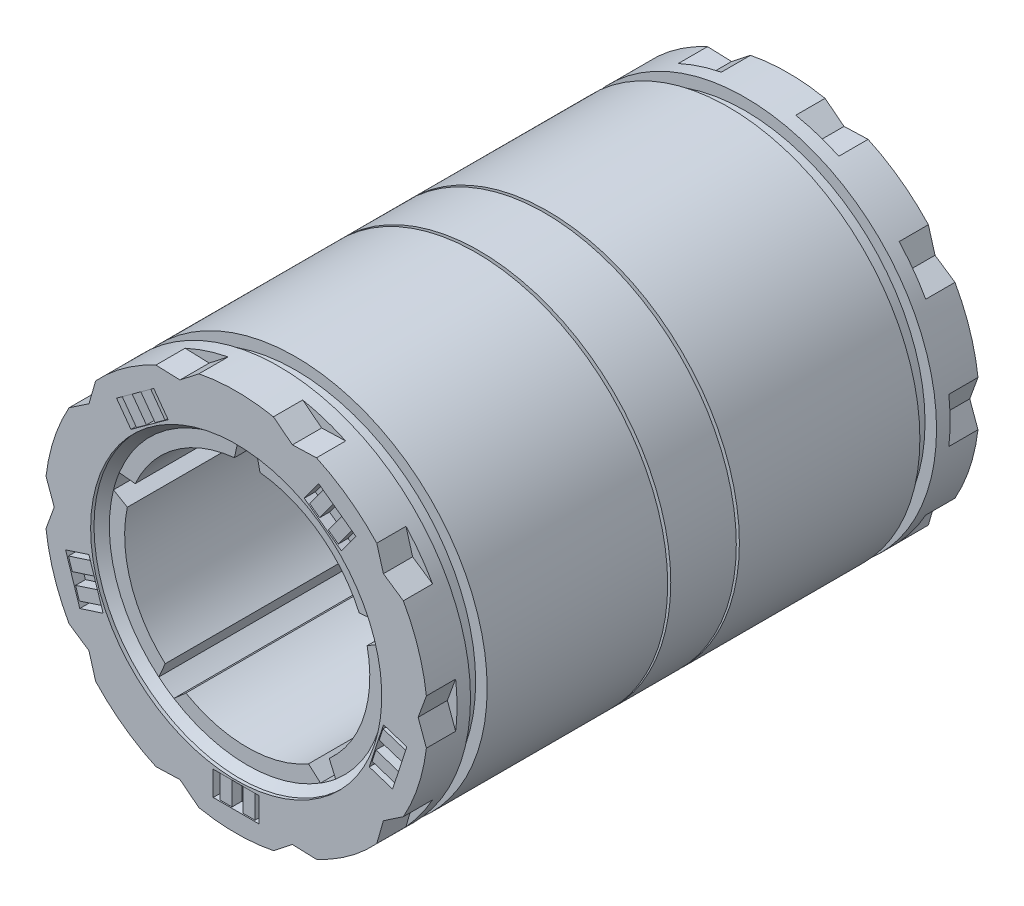
SolidWorks part; units mm, degrees
material "POM Acetal Copolymer"
ref_plane "Front Plane" through (0, 0, 0) normal (0, 0, 1) x (1, 0, 0)
ref_plane "Top Plane" through (0, 0, 0) normal (0, 1, 0) x (1, 0, 0)
ref_plane "Right Plane" through (0, 0, 0) normal (1, 0, 0) x (0, 0, -1)
sketch "Sketch1" plane through (0, 0, 0) normal (0, 0, 1) x (1, 0, 0)
  line L0 (0, 0) -> (-9.9219, -17.1852) construction
  line L2 (9.9219, -17.1852) -> (0, 0) construction
  circle A0 centre (0, 0) radius 19.8438
  circle A1 centre (0, 0) radius 12.7
  point P4 (-6.35, -10.9985)
  point P5 (6.35, -10.9985)
  dimension "OD" = 39.6875
  dimension "ID" = 25.4
  dimension "a" = 60
  dimension "Width" = 12.7
sketch "Sketch2" plane through (0, 0, 0) normal (1, 0, 0) x (0, 0, -1)
  line L0 (-28.575, 0) -> (28.575, 0) construction
  line L1 (0, -19.8438) -> (0, 19.8438) construction
  line L3 (-24.1427, 19.8438) -> (-22.4155, 19.8438)
  line L4 (-24.1427, 19.8438) -> (-24.1427, 18.6499)
  line L5 (-24.1427, 18.6499) -> (-22.4155, 18.6499)
  line L6 (-22.4155, 19.8438) -> (-22.4155, 18.6499)
  point P3 (-24.1427, 0)
  point P5 (24.1427, 0)
  point P10 (-22.4155, 0)
  dimension "Overall Length" = 57.15
  dimension "Retaining Ring Groove End to End Length" = 48.2854
  dimension "Groove Thickness" = 1.7272
  dimension "Groove Depth" = 1.1938
sketch "Sketch3" plane through (0, 0, 0) normal (1, 0, 0) x (0, 0, -1)
  line L0 (-28.575, 12.7) -> (-28.575, 19.8438)
  line L1 (-28.575, 19.8438) -> (-24.1427, 19.8438)
  line L2 (-24.1427, 19.8438) -> (-24.1427, 18.6499)
  line L3 (-24.1427, 18.6499) -> (-22.4155, 18.6499)
  line L4 (-22.4155, 18.6499) -> (-22.4155, 19.8438)
  line L5 (-22.4155, 19.8438) -> (-3.7148, 19.8438)
  line L6 (22.4155, 19.8438) -> (22.4155, 18.65)
  line L7 (22.4155, 18.65) -> (24.1427, 18.65)
  line L8 (24.1427, 18.65) -> (24.1427, 19.8438)
  line L9 (24.1427, 19.8438) -> (28.575, 19.8438)
  line L10 (28.575, 19.8438) -> (28.575, 12.7)
  line L11 (28.575, 12.7) -> (-28.575, 12.7)
  line L14 (-3.7148, 19.8438) -> (-3.7148, 19.05)
  line L15 (-3.7148, 19.05) -> (-3.3947, 19.05)
  line L16 (-3.3947, 19.05) -> (-3.3947, 19.8438)
  line L17 (3.3947, 19.8438) -> (3.3947, 19.05)
  line L18 (3.3947, 19.05) -> (3.7147, 19.05)
  line L19 (3.7147, 19.05) -> (3.7147, 19.8438)
  line L20 (-3.3947, 19.8438) -> (3.3947, 19.8438)
  line L21 (3.7147, 19.8438) -> (22.4155, 19.8438)
  point P17 (0, 12.7)
  point P30 (0, 19.8438)
  dimension "D1" = 7.4295
  dimension "D2" = 0.7937
  dimension "D3" = 0.32
revolve "Revolve1" add sketch "Sketch3" angle 360 about L0
sketch "Sketch4" plane through (0, 0, 0) normal (0, 0, 1) x (1, 0, 0)
  line L0 (-6.35, -10.9985) -> (-7.5961, -12.1009)
  line L2 (-12.4225, 2.6405) -> (-13.856, 3.4849)
  line L3 (6.35, -10.9985) -> (7.5961, -12.1009)
  line L5 (-8.498, -9.4379) -> (-9.1614, -10.9637)
  line L6 (-1.3275, 12.6304) -> (-0.9674, 14.2547)
  line L7 (-11.602, 5.1656) -> (-13.2581, 5.325)
  line L8 (11.602, 5.1656) -> (13.2581, 5.325)
  line L9 (1.3275, 12.6304) -> (0.9674, 14.2547)
  line L10 (8.498, -9.4379) -> (9.1614, -10.9637)
  line L11 (12.4225, 2.6405) -> (13.856, 3.4849)
  arc A0 (0.9674, 14.2547) -> (-0.9674, 14.2547) centre (0, 0) ccw
  circle A1 centre (0, 0) radius 12.7 construction
  arc A2 (-11.602, 5.1656) -> (-12.4225, 2.6405) centre (0, 0) ccw
  arc A11 (-13.2581, 5.325) -> (-13.856, 3.4849) centre (0, 0) ccw
  arc A12 (-13.856, 3.4849) -> (-9.1614, -10.9637) centre (0, 0) ccw construction
  arc A13 (9.1614, -10.9637) -> (13.856, 3.4849) centre (0, 0) ccw construction
  arc A14 (13.2581, 5.325) -> (0.9674, 14.2547) centre (0, 0) ccw construction
  arc A15 (8.498, -9.4379) -> (12.4225, 2.6405) centre (0, 0) ccw construction
  arc A16 (11.602, 5.1656) -> (1.3275, 12.6304) centre (0, 0) ccw construction
  arc A17 (-1.3275, 12.6304) -> (-11.602, 5.1656) centre (0, 0) ccw construction
  arc A18 (-12.4225, 2.6405) -> (-8.498, -9.4379) centre (0, 0) ccw construction
  arc A19 (-0.9674, 14.2547) -> (-13.2581, 5.325) centre (0, 0) ccw construction
  arc A20 (13.856, 3.4849) -> (13.2581, 5.325) centre (0, 0) ccw
  arc A21 (7.5961, -12.1009) -> (9.1614, -10.9637) centre (0, 0) ccw
  arc A22 (-9.1614, -10.9637) -> (-7.5961, -12.1009) centre (0, 0) ccw
  arc A23 (1.3275, 12.6304) -> (-1.3275, 12.6304) centre (0, 0) ccw
  arc A24 (12.4225, 2.6405) -> (11.602, 5.1656) centre (0, 0) ccw
  arc A25 (6.35, -10.9985) -> (8.498, -9.4379) centre (0, 0) ccw
  arc A26 (-8.498, -9.4379) -> (-6.35, -10.9985) centre (0, 0) ccw
  point P31 (0, 0)
  dimension "D1" = 1.5875
  dimension "D3" = 25
  dimension "D2" = 5
extrude "Cut-Extrude1" cut sketch "Sketch4" against normal through all both and the other way through all
sketch "Sketch5" plane through (0, 0, 0) normal (0, 0, 1) x (1, 0, 0)
  circle A0 centre (0, 0) radius 15.0813
  circle A1 centre (0, 0) radius 12.7 construction
  dimension "D1" = 2.3813
extrude "Cut-Extrude2" cut sketch "Sketch5" against normal blind 1.143 from surface starting at face at (0, 0, 28.575)
extrude "Cut-Extrude3" cut sketch "Sketch5<2>" along normal blind 1.143 from surface starting at face at (19.8438, 0, -28.575)
sketch "Sketch5<2>" plane through (0, 0, 0) normal (0, 0, 1) x (1, 0, 0) same geometry as "Sketch5"
chamfer "Chamfer1" distance 0.7937 angle 45 2 edges at (-15.0813, 0, 27.432) (15.0813, 0, -27.432)
sketch "Sketch8" plane through (0, 0, 0) normal (0, 0, 1) x (1, 0, 0)
  line L0 (-8.3186, 18.016) -> (-5.8255, 17.9289)
  line L1 (-5.8255, 17.9289) -> (-3.8596, 19.4648)
  line L2 (0, 0) -> (0, 18.8516) construction
  line L3 (0, 0) -> (-5.8255, 17.9289) construction
  line L4 (3.8596, 19.4648) -> (5.8255, 17.9289)
  line L5 (5.8255, 17.9289) -> (8.3186, 18.016)
  line L6 (14.5636, 13.4787) -> (15.2512, 11.0807)
  line L7 (15.2512, 11.0807) -> (17.3194, 9.6857)
  line L8 (19.7048, 2.3442) -> (18.8516, 0)
  line L9 (18.8516, 0) -> (19.7048, -2.3442)
  line L10 (17.3194, -9.6857) -> (15.2512, -11.0807)
  line L11 (15.2512, -11.0807) -> (14.5636, -13.4787)
  line L12 (8.3186, -18.016) -> (5.8255, -17.9289)
  line L13 (5.8255, -17.9289) -> (3.8596, -19.4648)
  line L14 (-3.8596, -19.4648) -> (-5.8255, -17.9289)
  line L15 (-5.8255, -17.9289) -> (-8.3186, -18.016)
  line L16 (-14.5636, -13.4787) -> (-15.2512, -11.0807)
  line L17 (-15.2512, -11.0807) -> (-17.3194, -9.6857)
  line L18 (-19.7048, -2.3442) -> (-18.8516, 0)
  line L19 (-18.8516, 0) -> (-19.7048, 2.3442)
  line L20 (-17.3194, 9.6857) -> (-15.2512, 11.0807)
  line L21 (-15.2512, 11.0807) -> (-14.5636, 13.4787)
  circle A0 centre (0, 0) radius 19.8438 construction
  circle A1 centre (0, 0) radius 18.8516 construction
  arc A2 (-3.8596, 19.4648) -> (-8.3186, 18.016) centre (0, 0) ccw
  arc A3 (8.3186, 18.016) -> (3.8596, 19.4648) centre (0, 0) ccw
  arc A4 (17.3194, 9.6857) -> (14.5636, 13.4787) centre (0, 0) ccw
  arc A5 (19.7048, -2.3442) -> (19.7048, 2.3442) centre (0, 0) ccw
  arc A6 (14.5636, -13.4787) -> (17.3194, -9.6857) centre (0, 0) ccw
  arc A7 (3.8596, -19.4648) -> (8.3186, -18.016) centre (0, 0) ccw
  arc A8 (-8.3186, -18.016) -> (-3.8596, -19.4648) centre (0, 0) ccw
  arc A9 (-17.3194, -9.6857) -> (-14.5636, -13.4787) centre (0, 0) ccw
  arc A10 (-19.7048, 2.3442) -> (-19.7048, -2.3442) centre (0, 0) ccw
  arc A11 (-14.5636, 13.4787) -> (-17.3194, 9.6857) centre (0, 0) ccw
  point P38 (0, 0)
  dimension "D1" = 140
  dimension "D2" = 0.9922
  dimension "D3" = 10
extrude "Cut-Extrude5" cut sketch "Sketch8" against normal blind 3.029 from surface starting at face at (-15.0813, 0, 28.575)
extrude "Cut-Extrude6" cut sketch "Sketch8<2>" along normal blind 3.029 from surface starting at face at (15.0813, 0, -28.575)
sketch "Sketch8<2>" plane through (0, 0, 0) normal (0, 0, 1) x (1, 0, 0) same geometry as "Sketch8"
sketch "Sketch9" plane through (0, 0, 0) normal (0, 0, 1) x (1, 0, 0)
  line L0 (0, -19.8438) -> (0, -17.8117) construction
  line L1 (-2.3813, -15.2718) -> (-1.8256, -15.2718)
  line L2 (-2.3813, -15.2718) -> (-2.3813, -17.8117)
  line L3 (-2.3813, -17.8117) -> (-1.8256, -17.8117)
  line L4 (2.3813, -15.2718) -> (2.3813, -17.8117)
  line L5 (-1.8256, -15.2718) -> (-1.8256, -17.8117)
  line L6 (-2.3813, -16.5418) -> (-1.8256, -16.5418) construction
  line L7 (-0.5556, -15.2718) -> (-0.5556, -17.8117)
  line L8 (-1.8256, -16.5418) -> (-0.5556, -16.5418) construction
  line L9 (0.5556, -15.2718) -> (0.5556, -17.8117)
  line L10 (-0.5556, -16.5418) -> (0, -16.5418) construction
  line L11 (1.8256, -15.2718) -> (1.8256, -17.8117)
  line L12 (0.5556, -16.5418) -> (1.8256, -16.5418) construction
  line L13 (1.8256, -16.5418) -> (2.3813, -16.5418) construction
  line L14 (0, -16.5418) -> (0.5556, -16.5418) construction
  line L15 (-0.5556, -15.2718) -> (0.5556, -15.2718)
  line L16 (1.8256, -15.2718) -> (2.3813, -15.2718)
  line L17 (1.8256, -17.8117) -> (2.3813, -17.8117)
  line L18 (-0.5556, -17.8117) -> (0.5556, -17.8117)
  circle A1 centre (0, 0) radius 19.8438 construction
  dimension "D1" = 4.7625
  dimension "D2" = 2.54
  dimension "D3" = 2.032
  dimension "D4" = 1.27
extrude "Cut-Extrude7" cut sketch "Sketch9" against normal blind 1.143 from surface starting at face at (-15.0813, 0, 28.575)
sketch "Sketch10" plane through (0, 0, 0) normal (0, 0, 1) x (1, 0, 0)
  line L1 (-2.3813, -15.2718) -> (2.3812, -15.2718)
  line L2 (-2.3813, -15.2718) -> (-2.3812, -17.8117)
  line L3 (-2.3812, -17.8117) -> (2.3813, -17.8117)
  line L4 (2.3812, -15.2718) -> (2.3813, -17.8117)
extrude "Cut-Extrude8" cut sketch "Sketch10" against normal blind 0.127 from surface starting at face at (-2.1034, -16.5418, 28.575)
extrude "Cut-Extrude9" cut sketch "Sketch9<2>" along normal blind 1.143 from surface starting at face at (15.0813, 0, -28.575)
sketch "Sketch9<2>" plane through (0, 0, 0) normal (0, 0, 1) x (1, 0, 0) same geometry as "Sketch9"
extrude "Cut-Extrude11" cut sketch "Sketch10<2>" along normal blind 0.127 from surface starting at face at (2.1034, -16.5418, -28.575)
sketch "Sketch10<2>" plane through (0, 0, 0) normal (0, 0, 1) x (1, 0, 0) same geometry as "Sketch10"
pattern_circular "CirPattern2" count 5 over 360 about axis through (0, 0, 28.575) along (0, 0, 1) of "Cut-Extrude7", "Cut-Extrude8", "Cut-Extrude9", "Cut-Extrude11"
sketch "Sketch6" [suppressed] plane through (0, 0, 0) normal (0, 1, 0) x (1, 0, 0)
  line L0 (-2.54, 21.6535) -> (-2.54, -21.6535)
  line L1 (-3.81, 21.6535) -> (-3.81, -21.6535)
  line L2 (-3.81, -22.9235) -> (-3.81, -21.6535) construction
  line L3 (-2.54, 0) -> (-3.81, 0) construction
  line L4 (-6.35, 0) -> (-3.175, 0) construction
  line L5 (-6.35, 27.432) -> (-6.35, -27.432) construction
  line L6 (-3.175, 0) -> (0, 0) construction
  line L7 (0, 0) -> (3.175, 0) construction
  line L8 (3.175, 0) -> (6.35, 0) construction
  line L9 (6.35, 27.432) -> (6.35, -27.432) construction
  line L10 (0, -28.575) -> (0, 28.575) construction
  line L11 (0, -28.575) -> (0, 28.575) construction
  line L12 (2.54, 0) -> (3.81, 0) construction
  line L13 (3.81, -22.9235) -> (3.81, -21.6535) construction
  line L14 (3.81, 21.6535) -> (3.81, -21.6535)
  line L15 (2.54, 21.6535) -> (2.54, -21.6535)
  arc A0 (-3.81, -21.6535) -> (-3.81, -22.9235) centre (-3.81, -22.2885) ccw
  arc A1 (-2.54, -21.6535) -> (-3.81, -22.9235) centre (-3.81, -21.6535) cw
  arc A2 (-3.81, 21.6535) -> (-3.81, 22.9235) centre (-3.81, 22.2885) cw
  arc A3 (-2.54, 21.6535) -> (-3.81, 22.9235) centre (-3.81, 21.6535) ccw
  arc A4 (2.54, 21.6535) -> (3.81, 22.9235) centre (3.81, 21.6535) cw
  arc A5 (3.81, 21.6535) -> (3.81, 22.9235) centre (3.81, 22.2885) ccw
  arc A6 (2.54, -21.6535) -> (3.81, -22.9235) centre (3.81, -21.6535) ccw
  arc A7 (3.81, -21.6535) -> (3.81, -22.9235) centre (3.81, -22.2885) cw
  point P7 (-2.54, 0)
  point P8 (-3.81, 0)
  point P11 (-3.175, 0)
  dimension "D1" = 1.27
  dimension "D2" = 22.2885
extrude "Cut-Extrude4" [suppressed] cut sketch "Sketch6" against normal up to surface (14.0599 mm away)
sketch "Sketch7" [suppressed] plane through (0, 0, 0) normal (0, 0, 1) x (1, 0, 0)
  line L0 (0, -12.7) -> (0, -14.2875) construction
  line L1 (-2.54, 0) -> (-2.54, -13.2525) construction
  line L2 (-3.81, 0) -> (-3.81, -12.9447) construction
  line L3 (-3.81, -12.9447) -> (-3.1787, -13.114) construction
  line L4 (-3.1787, -13.114) -> (-2.54, -13.2525) construction
  line L6 (-3.9366, -12.878) -> (-2.4045, -13.2889)
  line L8 (-3.1787, -13.114) -> (-3.1705, -13.0834) construction
  circle A0 centre (0, 0) radius 13.4938 construction
  arc A1 (-6.35, -10.9985) -> (6.35, -10.9985) centre (0, 0) ccw construction
  arc A2 (-7.5961, -12.1009) -> (7.5961, -12.1009) centre (0, 0) ccw construction
  circle A3 centre (-3.1787, -13.114) radius 0.7937 construction
  arc A5 (-2.4045, -13.2889) -> (-3.9366, -12.878) centre (-3.1787, -13.114) ccw
  point P11 (0, -13.4938)
revolve "Revolve3" [suppressed] add sketch "Sketch7" angle 360 about L6
pattern_linear "LPattern1" [suppressed] count 15 spacing 1.5875 along (0, 0, 1) count 15 spacing 1.5875 along (0, 0, -1) of bodies 110
mirror "Mirror1" [suppressed] about plane through (0, 0, 0) normal (1, 0, 0)
pattern_circular "CirPattern1" [suppressed] count 5 over 360 about axis through (0, 0, 28.575) along (0, 0, -1) of bodies 112
equation "\"D1@Sketch3\"=\"Overall Length@Sketch2\"*.13"
equation "\"D2@Sketch3\"=\"OD@Sketch1\"*.02"
equation "\"D3@Sketch3\"=\"Overall Length@Sketch2\"*.0056"
equation "\"D1@Sketch4\"=\"OD@Sketch1\"*.04"
equation "\"D1@Sketch5\"=\"OD@Sketch1\"*.06"
equation "\"D1@Cut-Extrude2\"=.02*\"Overall Length@Sketch2\""
equation "\"D1@Cut-Extrude3\"=.02*\"Overall Length@Sketch2\""
equation "\"D1@Sketch6\"= .08*.4*\"OD@Sketch1\""
equation "\"D2@Sketch6\"=.39*\"Overall Length@Sketch2\""
equation "\"D1@Chamfer1\"=\"OD@Sketch1\"*.02"
equation "\"D4@LPattern1\"=\"Overall Length@Sketch2\"* .0277777778"
equation "\"D3@LPattern1\"=\"Overall Length@Sketch2\"* .0277777778"
equation "\"D2@Sketch8\"=\"OD@Sketch1\"*.025"
equation "\"D1@Cut-Extrude5\"=.053*\"Overall Length@Sketch2\""
equation "\"D1@Cut-Extrude6\"=.053*\"Overall Length@Sketch2\""
equation "\"D1@Sketch9\"=\"OD@Sketch1\"*.12"
equation "\"D2@Sketch9\"=\"OD@Sketch1\"*.064"
equation "\"D3@Sketch9\"=\"OD@Sketch1\"*.0512"
equation "\"D4@Sketch9\"=\"OD@Sketch1\"* .032"
equation "\"D1@Cut-Extrude7\"=.02*\"Overall Length@Sketch2\""
equation "\"D1@Cut-Extrude9\"=.02*\"Overall Length@Sketch2\""
